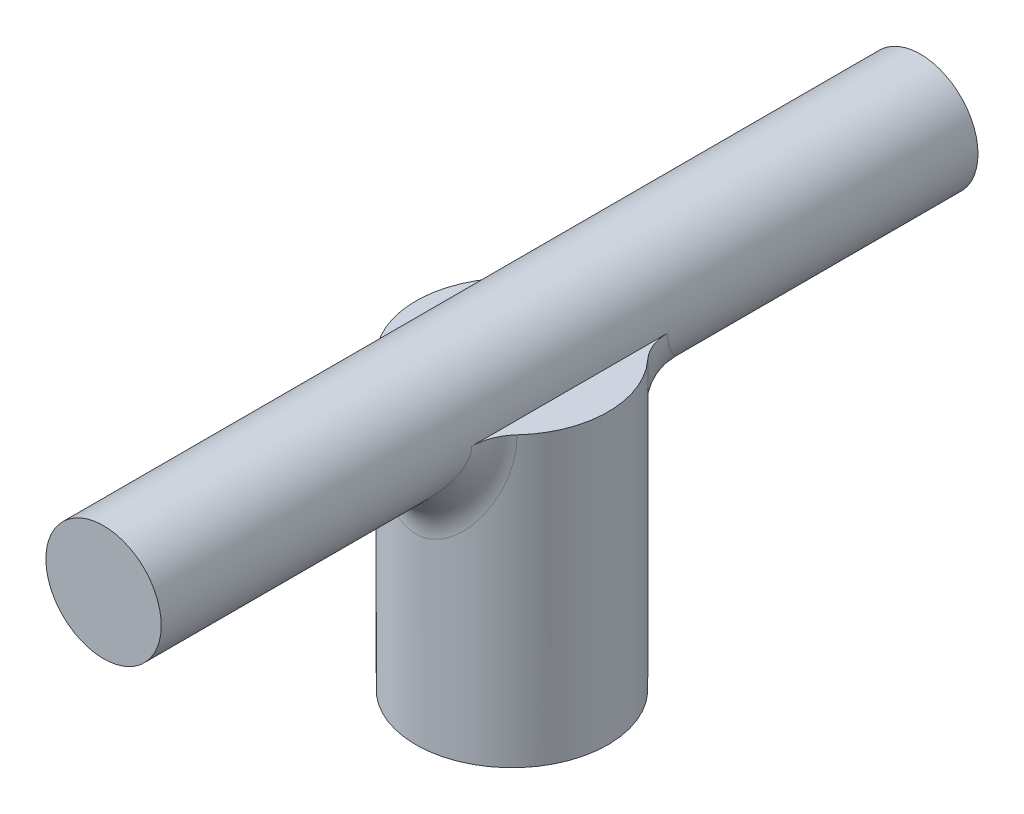
SolidWorks part; units mm, degrees
ref_plane "Front Plane" through (0, 0, 0) normal (0, 0, 1) x (1, 0, 0)
ref_plane "Top Plane" through (0, 0, 0) normal (0, 1, 0) x (1, 0, 0)
ref_plane "Right Plane" through (0, 0, 0) normal (1, 0, 0) x (0, 0, -1)
sketch "Sketch1" plane through (0, 0, 0) normal (0, 1, 0) x (1, 0, 0)
  circle A0 centre (0, 0) radius 10
  dimension "D1" = 20
extrude "Boss-Extrude1" add sketch "Sketch1" along normal blind 30 contours A0
sketch "Sketch2" plane through (0, 0, 0) normal (0, 0, 1) x (1, 0, 0)
  line L0 (10, 30) -> (-10, 30) construction
  circle A0 centre (0, 30) radius 6
  dimension "D1" = 12
extrude "Boss-Extrude2" add sketch "Sketch2" along normal mid plane 85
fillet "Fillet1" radius 5 2 edges at (0.1657, 24.0023, -9.9986) (0.2154, 24.0039, 9.9977)
